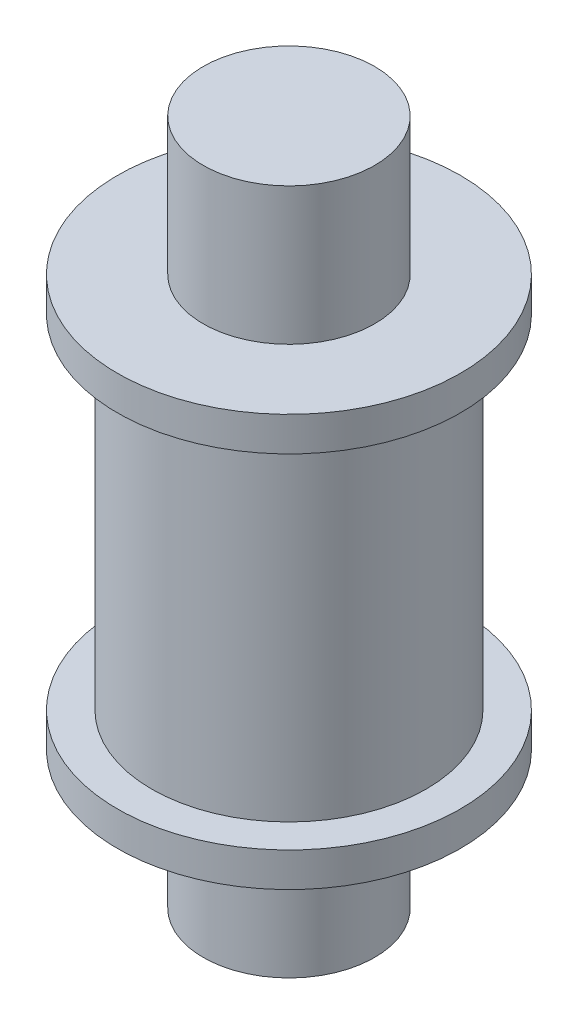
SolidWorks part; units mm, degrees
other "Camera1"
material "Commercial Bronze, UNS C22000 (90-10 Bronze)"
ref_plane "Plan de face" through (0, 0, 0) normal (0, 0, 1) x (1, 0, 0)
ref_plane "Plan de dessus" through (0, 0, 0) normal (0, 1, 0) x (1, 0, 0)
ref_plane "Plan de droite" through (0, 0, 0) normal (1, 0, 0) x (0, 0, -1)
sketch "Sketch1" plane through (0, 0, 0) normal (0, 0, 1) x (1, 0, 0)
  line L0 (10, -20) -> (0, -20)
  line L1 (10, -20) -> (10, 20)
  line L2 (0, -20) -> (0, 20)
  line L3 (10, 20) -> (0, 20)
  line L4 (10, -20) -> (0, 20) construction
  line L5 (0, -20) -> (10, 20) construction
  line L6 (5, 20) -> (5, 12)
  line L7 (5, 12) -> (10, 12)
  line L8 (10, 10) -> (8, 10)
  line L9 (8, 10) -> (8, -10)
  line L10 (0, 0) -> (10, 0) construction
  line L11 (10, -10) -> (8, -10)
  line L12 (5, -12) -> (10, -12)
  line L13 (5, -20) -> (5, -12)
  point P1 (5, 0)
  point P16 (8, 0)
  dimension "D1" = 5
  dimension "D2" = 40
  dimension "D3" = 8
  dimension "D4" = 20
  dimension "D5" = 10
  dimension "D6" = 8
revolve "Revolve1" add sketch "Sketch1" angle 360 about L2 region at (3.7143, 0, 0)
